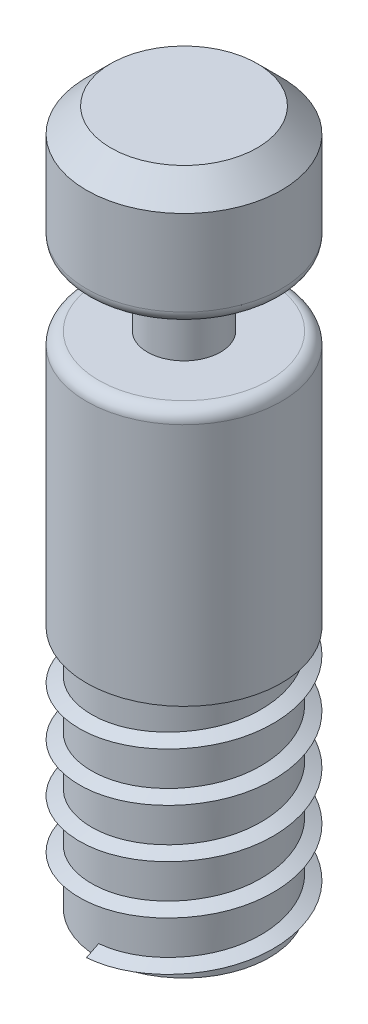
SolidWorks part; units mm, degrees
ref_plane "Front Plane" through (0, 0, 0) normal (0, 0, 1) x (1, 0, 0)
ref_plane "Top Plane" through (0, 0, 0) normal (0, 1, 0) x (1, 0, 0)
ref_plane "Right Plane" through (0, 0, 0) normal (1, 0, 0) x (0, 0, -1)
sketch "Sketch1" plane through (0, 0, 0) normal (1, 0, 0) x (0, 0, -1)
  line L0 (0, 0) -> (-3, 0)
  line L1 (-4, -1) -> (-4, -4.5)
  line L2 (-3.5, -5) -> (-1.5, -5)
  line L3 (-1.5, -5) -> (-1.5, -8)
  line L4 (-1.5, -8) -> (-3.5, -8)
  line L5 (-4, -8.5) -> (-4, -18.5)
  line L6 (-3.5, -28.5) -> (0, -28.5)
  line L7 (-3, 0) -> (-4, -1)
  line L8 (0, 5.0807) -> (0, -5.0807) construction
  line L9 (0, 0) -> (0, -28.5) construction
  line L10 (0, 0) -> (0, -28.5)
  line L11 (-4, -18.5) -> (-3.5, -18.5)
  line L12 (-3.5, -18.5) -> (-3.5, -28.5)
  arc A0 (-3.5, -5) -> (-4, -4.5) centre (-3.5, -4.5) cw
  arc A1 (-4, -8.5) -> (-3.5, -8) centre (-3.5, -8.5) cw
  point P1 (-4, 0)
  point P14 (-4, -5)
  point P17 (-4, -8)
  dimension "D6" = 0.5
  dimension "D1" = 4
  dimension "D2" = 5
  dimension "D3" = 3
  dimension "D4" = 10
  dimension "D5" = 2.5
  dimension "D7" = 0.5
  dimension "D9" = 10
revolve "Revolve1" add sketch "Sketch1" angle 360 about L9
sketch "Sketch3" plane through (0, 0, 0) normal (1, 0, 0) x (0, 0, -1)
  line L0 (-3.5, -28.5) -> (-4, -28.25)
  line L1 (-4, -28.25) -> (-3.5, -28)
  line L2 (-3.5, -18.5) -> (-3.5, -28.5) construction
  line L3 (-3.5, -28) -> (-3.5, -28.5)
  dimension "D1" = 0.5
  dimension "D2" = 0.5
sketch "Sketch4" plane through (0, -28.5, 0) normal (0, -1, 0) x (1, 0, 0)
  circle A0 centre (0, 0) radius 3.5 construction
  circle A1 centre (0, 0) radius 3.5
curve "Helix/Spiral1" pitch 2 height 10 turns 5
sweep "Sweep1" add profiles "Sketch3" path "Helix/Spiral1"
